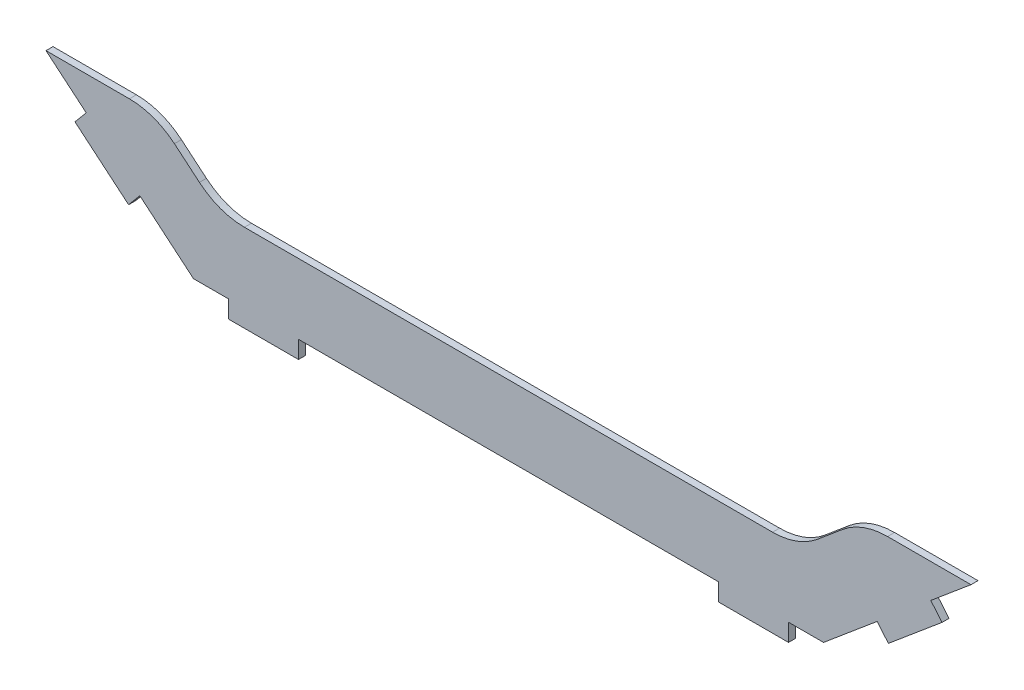
SolidWorks part; units mm, degrees
material "PBT General Purpose"
ref_plane "Front Plane" through (0, 0, 0) normal (0, 0, 1) x (1, 0, 0)
ref_plane "Top Plane" through (0, 0, 0) normal (0, 1, 0) x (1, 0, 0)
ref_plane "Right Plane" through (0, 0, 0) normal (1, 0, 0) x (0, 0, -1)
sketch "frame_outline" plane through (0, 0, 0) normal (0, 0, 1) x (1, 0, 0)
  line L89 (0, 0) -> (3, 0)
  line L99 (3, 0) -> (3, -0.25)
  line L100 (3, -0.25) -> (4, -0.25)
  line L101 (4, -0.25) -> (4, 0)
  line L102 (4, 0) -> (4.5, 0)
  line L103 (4.5, 0) -> (5.266, 0.6428)
  line L104 (5.266, 0.6428) -> (5.4267, 0.4513)
  line L105 (5.4267, 0.4513) -> (6.1928, 1.0941)
  line L106 (6.1928, 1.0941) -> (6.0321, 1.2856)
  line L107 (6.0321, 1.2856) -> (6.6066, 1.7677)
  line L108 (6.6066, 1.7677) -> (5.0509, 1.7677)
  line L109 (5.0509, 1.7677) -> (4.136, 1)
  line L110 (4.136, 1) -> (-4.136, 1)
  line L111 (0, 0) -> (-3, 0)
  line L112 (-3, 0) -> (-3, -0.25)
  line L113 (-3, -0.25) -> (-4, -0.25)
  line L114 (-4, -0.25) -> (-4, 0)
  line L115 (-4, 0) -> (-4.5, 0)
  line L116 (-4.5, 0) -> (-5.266, 0.6428)
  line L117 (-5.266, 0.6428) -> (-5.4267, 0.4513)
  line L118 (-5.4267, 0.4513) -> (-6.1928, 1.0941)
  line L119 (-6.1928, 1.0941) -> (-6.0321, 1.2856)
  line L120 (-6.0321, 1.2856) -> (-6.6066, 1.7677)
  line L121 (-6.6066, 1.7677) -> (-5.0509, 1.7677)
  line L122 (-5.0509, 1.7677) -> (-4.136, 1)
  dimension "D1" = 3
  dimension "D2" = 1
  dimension "D3" = 0.5
  dimension "D4" = 1
  dimension "D5" = 0.25
  dimension "D6" = 0.25
  dimension "D7" = 0.25
  dimension "D8" = 140
  dimension "D9" = 1
  dimension "D10" = 140
  dimension "D11" = 1
  dimension "D12" = 0.75
  dimension "D13" = 1
  dimension "D14" = 1
extrude "Boss-Extrude1" add sketch "frame_outline" along normal mid plane 0.1
fillet "Fillet1" radius 1 4 edges at (4.136, 1, 0) (5.0509, 1.7677, 0) (-4.136, 1, 0) (-5.0509, 1.7677, 0)
equation "\"t\"= 0.25'thickness of the sheets"
equation "\"t_cf\"= 0.115'thickness of single carbon fiber layer"
equation "\"t_kapton\"= 0.025'thickness of single Kapton flex layer"
equation "\"t_fr4\"= 0.1'thickness of FR4 with copper layer"
equation "\"joint_flex\"= 0.1'Width of flextures gap"
equation "\"joint_flex_eff\"= 0.02'Width of flecture after castelation"
equation "\"joint_fold\"= 0.2'Width of folding joints for 90deg fold"
equation "\"gap_tolerance\"= 0.002'Width to have interfecence fit between carbon fiber inserts"
equation "\"assemble_angle\"= 90'Angle of assembly parts"
equation "\"D1@Boss-Extrude1\"=0.1"
equation "\"link_lift\"= 0.5'Actuation linkage amplification for the lift motion"
equation "\"link_swing\"= 0.45'Actuation linkage amplification for the swing motion"
